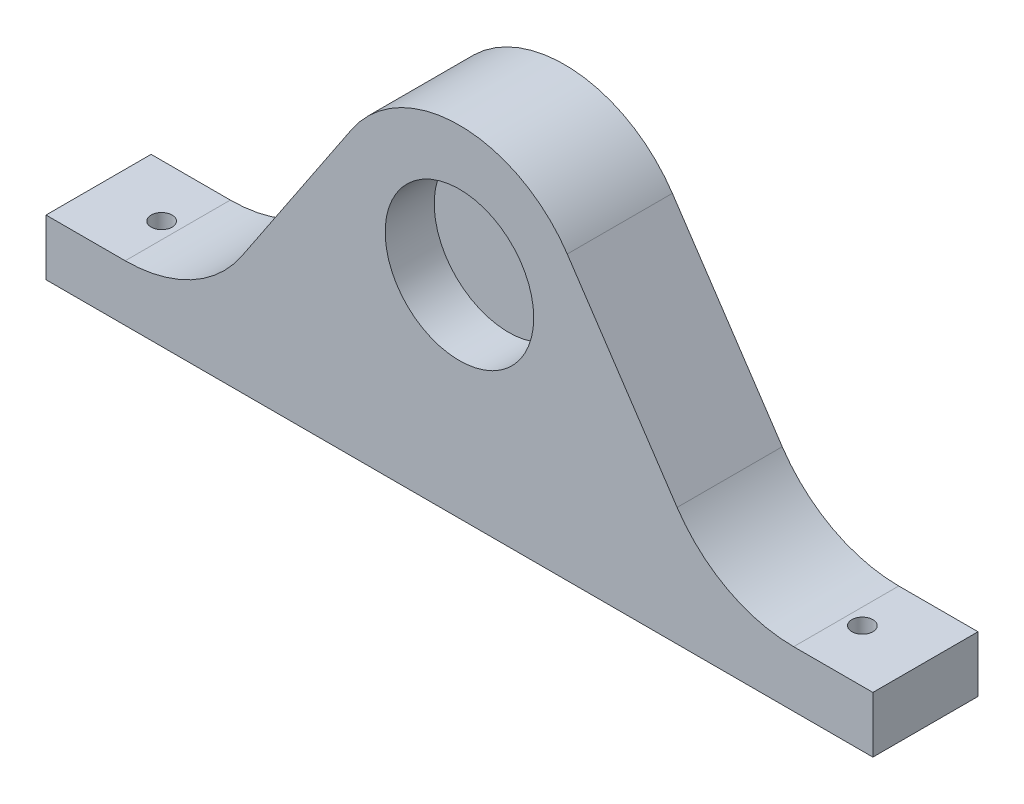
SolidWorks part; units mm, degrees
ref_plane "Front Plane" through (0, 0, 0) normal (0, 0, 1) x (1, 0, 0)
ref_plane "Top Plane" through (0, 0, 0) normal (0, 1, 0) x (1, 0, 0)
ref_plane "Right Plane" through (0, 0, 0) normal (1, 0, 0) x (0, 0, -1)
sketch "Sketch4" plane through (0, 0, 0) normal (0, 0, 1) x (1, 0, 0)
  line L0 (0, -18.5) -> (0, -30.1) construction
  line L1 (-59, -30.1) -> (59, -30.1)
  line L2 (59, -30.1) -> (59, -22.1)
  line L3 (59, -22.1) -> (47.6948, -22.1)
  line L4 (31.0614, -13.2055) -> (15.3858, 10.2726)
  line L5 (-59, -30.1) -> (-59, -22.1)
  line L6 (-59, -22.1) -> (-47.6948, -22.1)
  line L7 (-31.0614, -13.2055) -> (-15.3858, 10.2726)
  circle A0 centre (0, 0) radius 10.6
  arc A1 (15.3858, 10.2726) -> (-15.3858, 10.2726) centre (0, 0) ccw
  arc A2 (47.6948, -22.1) -> (31.0614, -13.2055) centre (47.6948, -2.1) cw
  arc A3 (-47.6948, -22.1) -> (-31.0614, -13.2055) centre (-47.6948, -2.1) ccw
  point P9 (0, -30.1)
  dimension "D1" = 21.2
  dimension "D2" = 37
  dimension "D3" = 20
extrude "Boss-Extrude3" add sketch "Sketch4" along normal blind 15
sketch "Sketch5" plane through (0, -30.1, 0) normal (0, -1, 0) x (1, 0, 0)
  line L0 (0, 0) -> (0, 7.5) construction
  line L1 (-50, 7.5) -> (50, 7.5) construction
  circle A0 centre (50, 7.5) radius 1.5
  circle A1 centre (-50, 7.5) radius 1.5
extrude "Cut-Extrude2" cut sketch "Sketch5" against normal blind 15
extrude "Boss-Extrude4" add sketch "Sketch4<2>" along normal blind 8 contours A0
sketch "Sketch4<2>" plane through (0, 0, 0) normal (0, 0, 1) x (1, 0, 0) same geometry as "Sketch4"
